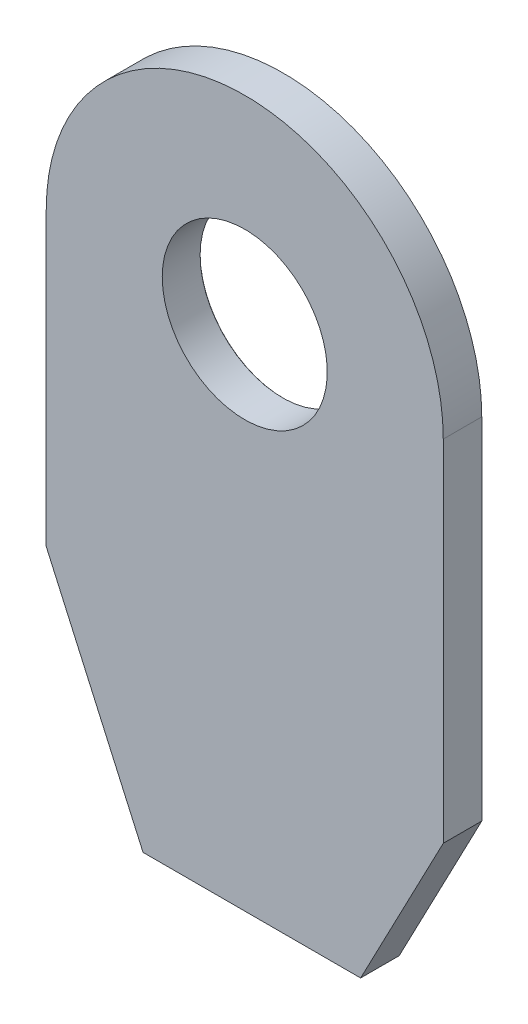
SolidWorks part; units mm, degrees
ref_plane "Front Plane" through (0, 0, 0) normal (0, 0, 1) x (1, 0, 0)
ref_plane "Top Plane" through (0, 0, 0) normal (0, 1, 0) x (1, 0, 0)
ref_plane "Right Plane" through (0, 0, 0) normal (1, 0, 0) x (0, 0, -1)
sketch "Sketch1" plane through (0, 0, 0) normal (0, 0, 1) x (1, 0, 0)
  line L0 (-7.94, 0) -> (-7.94, -20.32)
  line L1 (-7.94, -20.32) -> (7.94, -20.32)
  line L2 (7.94, -20.32) -> (7.94, 0)
  line L3 (7.94, -14.0013) -> (4.6346, -20.32)
  line L4 (-4.0681, -20.32) -> (-7.94, -11.6613)
  circle A0 centre (0, 0) radius 7.94
  dimension "D1" = 15.88
  dimension "D2" = 20.32
extrude "Boss-Extrude1" add sketch "Sketch1" along normal blind 1.54 contours A0 L0 L1 L2 | A0 region at (0.2039, -12.5341, 0)
hole_wizard "M6 Clearance Hole1" positions "Sketch4" profile "Sketch3" hole size "M6" standard "ANSI Metric" end condition through all
sketch "Sketch4" plane through (0, 0, 0) normal (0, 0, -1) x (-1, 0, 0)
  point P0 (0, 0)
sketch "Sketch3" plane through (0, 0, 0) normal (1, 0, 0) x (0, 1, 0)
  line L0 (0, 0) -> (0, 1.54)
  line L1 (0, 1.54) -> (3.3, 1.54)
  line L2 (3.3, 1.54) -> (3.3, 0.025)
  line L3 (3.3, 0.025) -> (3.325, 0)
  line L5 (3.325, 0) -> (0, 0)
  line L6 (-3.3, 0.025) -> (-3.325, 0) construction
  line L11 (0, -6.35) -> (0, 107.95) construction
  dimension "Thru Hole Dia." = 6.6
  dimension "Thru Hole Depth" = 1.54
  dimension "Near C'Sink Dia." = 6.65
  dimension "Near C'Sink Angle" = 90
